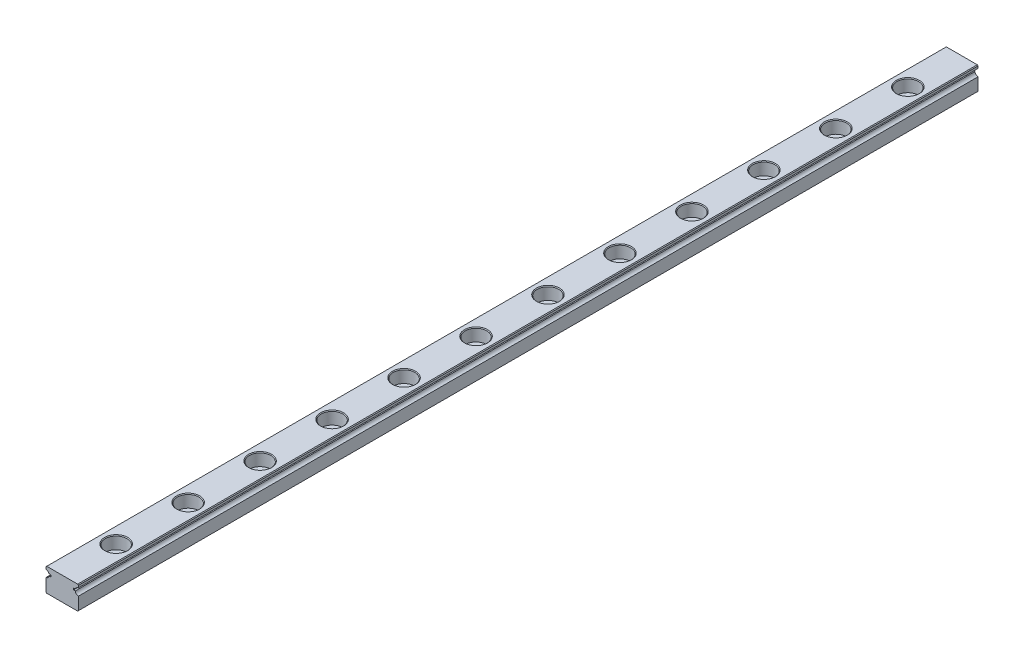
SolidWorks part; units mm, degrees
ref_plane "Front" through (0, 0, 0) normal (0, 0, 1) x (1, 0, 0)
ref_plane "Top" through (0, 0, 0) normal (0, 1, 0) x (1, 0, 0)
ref_plane "Right" through (0, 0, 0) normal (1, 0, 0) x (0, 0, -1)
sketch "Sketch1" plane through (0, 0, 0) normal (0, 0, 1) x (1, 0, 0)
  line L0 (0, 0) -> (0, 4.3706) construction
  line L1 (-4.3, -3.25) -> (4.3, -3.25)
  line L2 (-4.5, -3.05) -> (-4.5, 0.455)
  line L3 (-4.3, 3.25) -> (4.3, 3.25)
  line L4 (4.5, -3.05) -> (4.5, 0.455)
  line L5 (-4.5, -3.25) -> (4.5, 3.25) construction
  line L6 (-4.5, 3.25) -> (4.5, -3.25) construction
  line L7 (-4.5, 2.445) -> (-4.5, 3.05)
  line L8 (4.5, 2.445) -> (4.5, 3.05)
  line L9 (-4.5, -3.05) -> (-4.3, -3.25)
  line L10 (4.3, -3.25) -> (4.5, -3.05)
  line L11 (4.3, 3.25) -> (4.5, 3.05)
  line L12 (-4.5, 3.05) -> (-4.3, 3.25)
  line L13 (3.6177, 1.2625) -> (3.1501, 1.2625)
  line L14 (-3.6177, 1.2625) -> (-3.1501, 1.2625)
  line L15 (3.1501, 1.2625) -> (3.1501, 1.7625)
  line L16 (-3.6501, 1.7625) -> (-3.1501, 1.7625)
  line L17 (-3.1501, 1.2625) -> (-3.1501, 1.7625)
  line L18 (3.6501, 1.7625) -> (3.1501, 1.7625)
  arc A0 (-4.5, 2.445) -> (-3.6501, 1.7625) centre (-4.6, 1.45) cw
  arc A1 (4.5, 2.445) -> (3.6501, 1.7625) centre (4.6, 1.45) ccw
  arc A2 (-3.6177, 1.2625) -> (-4.5, 0.455) centre (-4.6, 1.45) cw
  arc A3 (3.6177, 1.2625) -> (4.5, 0.455) centre (4.6, 1.45) ccw
  point P0 (0, 0)
  dimension "D4" = 1
  dimension "D5" = 0.1
  dimension "D1" = 9
  dimension "D2" = 6.5
  dimension "D3" = 1.8
  dimension "D6" = 0.5
  dimension "D7" = 0.5
extrude "Extrude Rail Profile" add sketch "Sketch1" along normal blind 250
sketch "Sketch2" plane through (0, 3.25, 0) normal (0, 1, 0) x (1, 0, 0)
  line L0 (0, 0) -> (0, -15) construction
  circle A0 centre (0, -15) radius 1.75
  circle A1 centre (0, -15) radius 3
  dimension "D1" = 3.5
  dimension "D2" = 6
  dimension "D3" = 15
extrude "Extrude2" cut sketch "Sketch2" against normal up to next contours A0 region at (0, 3.25, 15)
extrude "Extrude4" cut sketch "Sketch" against normal blind 3.5
sketch "Sketch" plane through (0, 3.25, 0) normal (0, 1, 0) x (1, 0, 0) same geometry as "Sketch2"
chamfer "Chamfer1" distance 0.2 angle 45 2 edges at (0, -3.25, 16.75) (0, 3.25, 18)
pattern_linear "LPattern1" count 12 spacing 20 along (0, 0, 1) of "Extrude4", "Chamfer1", "Extrude2"
